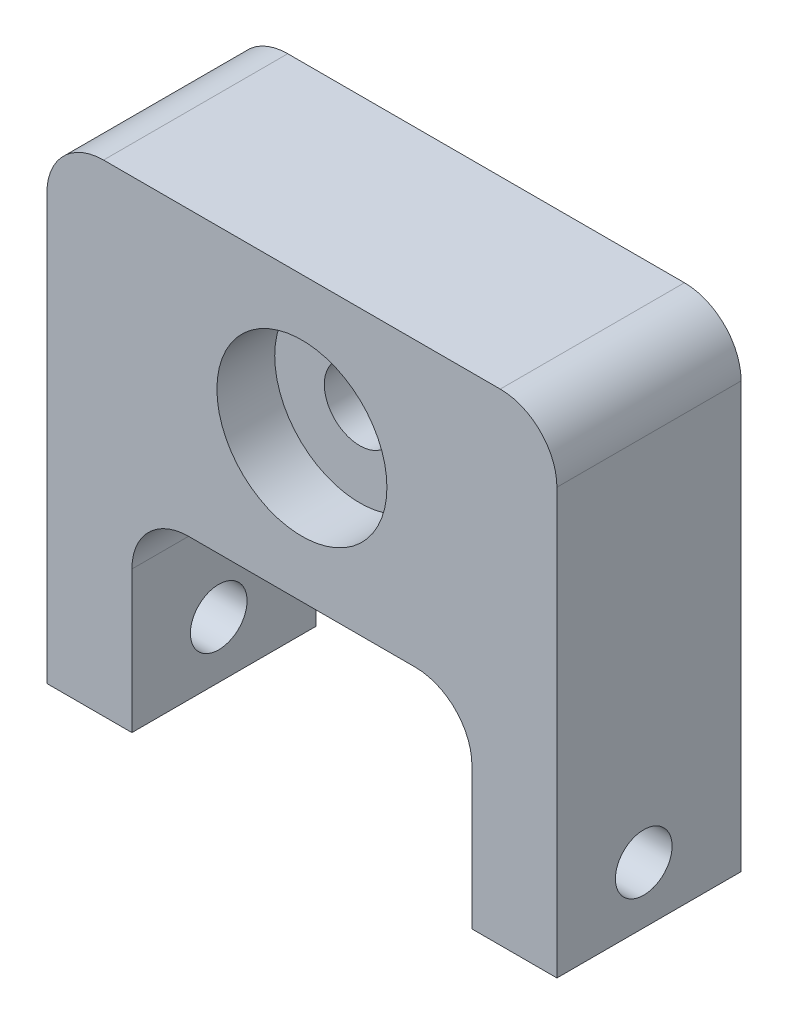
SolidWorks part; units mm, degrees
material "1060 Alloy"
ref_plane "Front" through (0, 0, 0) normal (0, 0, 1) x (1, 0, 0)
ref_plane "Top" through (0, 0, 0) normal (0, 1, 0) x (1, 0, 0)
ref_plane "Right" through (0, 0, 0) normal (1, 0, 0) x (0, 0, -1)
sketch "Sketch1" plane through (0, 0, 0) normal (0, 0, 1) x (1, 0, 0)
  line L1 (28.575, -15.875) -> (-28.575, -15.875)
  line L2 (28.575, -15.875) -> (28.575, 15.875)
  line L3 (28.575, 15.875) -> (-28.575, 15.875)
  line L4 (-28.575, -15.875) -> (-28.575, 15.875)
  line L5 (28.575, -15.875) -> (-28.575, 15.875) construction
  line L6 (28.575, 15.875) -> (-28.575, -15.875) construction
  point P0 (0, 0)
  dimension "D1" = 31.75
  dimension "D2" = 57.15
extrude "Boss-Extrude1" add sketch "Sketch1" along normal blind 20.6375
sketch "Sketch2" plane through (0, 0, 0) normal (0, 0, -1) x (-1, 0, 0)
  circle A0 centre (0, 0) radius 11.1125
  dimension "D1" = 22.225
extrude "Cut-Extrude1" cut sketch "Sketch2" against normal blind 6.985
sketch "Sketch3" plane through (0, 0, 6.985) normal (0, 0, -1) x (-1, 0, 0)
  circle A0 centre (0, 0) radius 8.255
  dimension "D1" = 16.51
extrude "Cut-Extrude2" cut sketch "Sketch3" against normal blind 2.413
sketch "Sketch4" plane through (0, 0, 9.398) normal (0, 0, -1) x (-1, 0, 0)
  circle A0 centre (0, 0) radius 3.9688
  dimension "D1" = 7.9375
extrude "Cut-Extrude3" cut sketch "Sketch4" against normal through all
sketch "Sketch6" plane through (0, 0, 9.398) normal (0, 0, -1) x (-1, 0, 0)
  circle A0 centre (0, 0) radius 9.525
  dimension "D1" = 19.05
extrude "Cut-Extrude4" cut sketch "Sketch6" against normal through all from offset 4.7625 offset against normal yes
sketch "Sketch7" plane through (0, -15.875, 0) normal (0, -1, 0) x (1, 0, 0)
  line L0 (-28.575, 0) -> (28.575, 0) construction
  line L1 (-28.575, 20.6375) -> (-19.05, 20.6375)
  line L2 (-28.575, 20.6375) -> (-28.575, 0)
  line L3 (-28.575, 0) -> (-19.05, 0)
  line L4 (-19.05, 20.6375) -> (-19.05, 0)
  line L6 (28.575, 20.6375) -> (19.05, 20.6375)
  line L7 (28.575, 20.6375) -> (28.575, 0)
  line L8 (28.575, 0) -> (19.05, 0)
  line L9 (19.05, 20.6375) -> (19.05, 0)
  dimension "D1" = 9.525
extrude "Boss-Extrude2" add sketch "Sketch7" along normal blind 22.225
sketch "Sketch9" plane through (28.575, 0, 0) normal (1, 0, 0) x (0, 0, -1)
  line L0 (0, -38.1) -> (-20.6375, -38.1) construction
  circle A0 centre (-10.9095, -31.75) radius 3.175
  dimension "D2" = 6.35
  dimension "D1" = 6.35
extrude "Cut-Extrude5" cut sketch "Sketch9" against normal through all
fillet "Fillet1" radius 6.35 4 edges at (28.575, 15.875, 10.3187) (-28.575, 15.875, 10.3187) (19.05, -15.875, 10.3187) (-19.05, -15.875, 10.3187)
